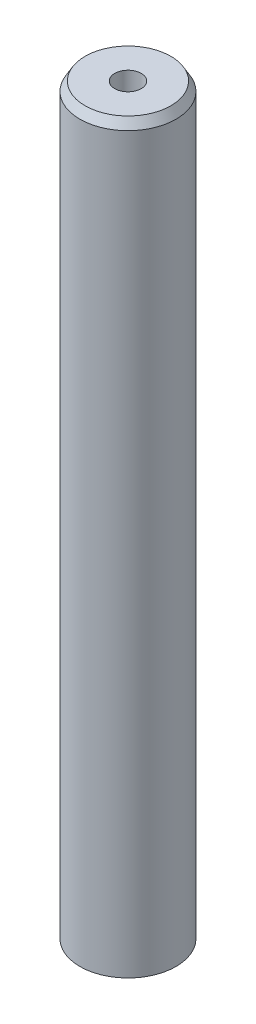
SolidWorks part; units mm, degrees
ref_plane "Front Plane" through (0, 0, 0) normal (0, 0, 1) x (1, 0, 0)
ref_plane "Top Plane" through (0, 0, 0) normal (0, 1, 0) x (1, 0, 0)
ref_plane "Right Plane" through (0, 0, 0) normal (1, 0, 0) x (0, 0, -1)
sketch "Sketch1" plane through (0, 0, 0) normal (0, 1, 0) x (1, 0, 0)
  circle A0 centre (0, 0) radius 10
  dimension "SHAFT_OD" = 20
extrude "Boss-Extrude1" add sketch "Sketch1" along normal blind 155.5381
sketch "Sketch2" plane through (0, 0, 0) normal (0, 1, 0) x (1, 0, 0)
  circle A0 centre (0, 0) radius 2.7547
  dimension "BORE_D" = 5.5093
extrude "Cut-Extrude1" cut sketch "Sketch2" along normal through all
chamfer "Chamfer1" distance 1.8772 angle 30 2 edges at (0, 155.5381, 10) (0, 0, 10) first distance on face at (0, 155.5381, 10) first distance on face at (0, 0, 2.7547)
